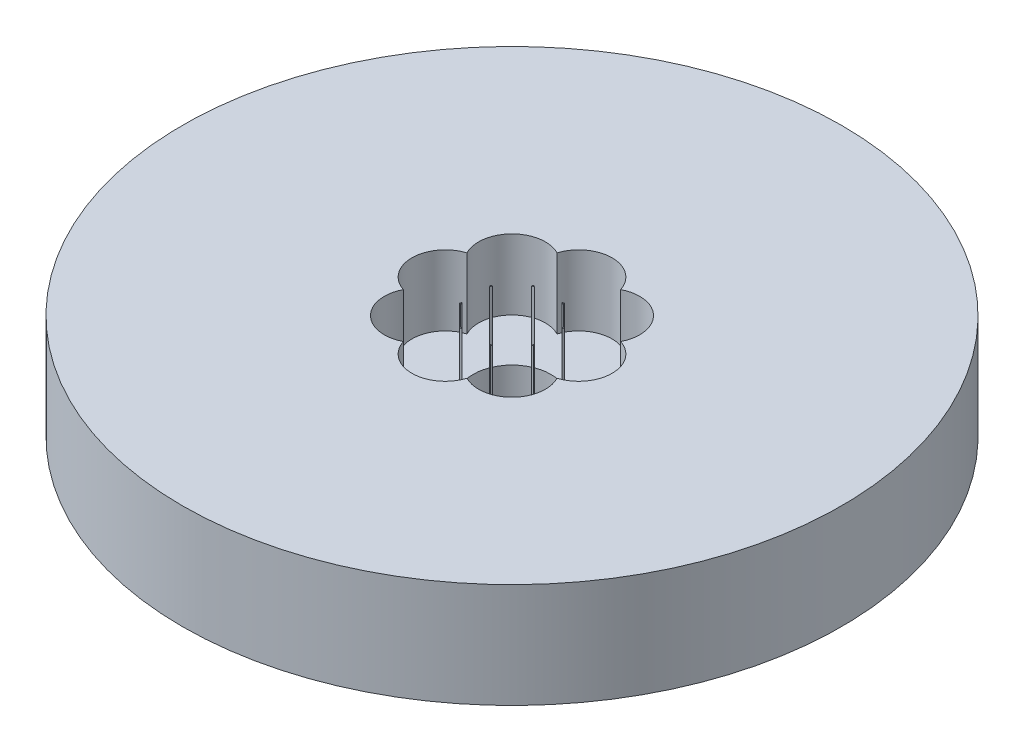
SolidWorks part; units mm, degrees
ref_plane "Front Plane" through (0, 0, 0) normal (0, 0, 1) x (1, 0, 0)
ref_plane "Top Plane" through (0, 0, 0) normal (0, 1, 0) x (1, 0, 0)
ref_plane "Right Plane" through (0, 0, 0) normal (1, 0, 0) x (0, 0, -1)
sketch "Sketch1" plane through (0, 0, 0) normal (0, 1, 0) x (1, 0, 0)
  circle A0 centre (0, 0) radius 85
  dimension "FLANGE_OD" = 170
extrude "Boss-Extrude1" add sketch "Sketch1" along normal blind 27
sketch "Sketch2" plane through (0, 0, 0) normal (0, 1, 0) x (1, 0, 0)
  circle A0 centre (0, 0) radius 10
  dimension "BORE_D" = 20
extrude "Cut-Extrude1" cut sketch "Sketch2" along normal through all
sketch "Sketch3" plane through (0, 27, 0) normal (0, 1, 0) x (1, 0, 0)
  circle A0 centre (0, 0) radius 17.2007 construction
  circle A1 centre (-17.2007, 0) radius 8.6113
  dimension "BOLT_D" = 17.2227
  dimension "BOLT_PCD" = 34.4013
extrude "Cut-Extrude2" cut sketch "Sketch3" against normal blind 18.1211
pattern_circular "CirPattern1" count 8 over 360 about axis through (0, 0, 0) along (0, 1, 0) of "Cut-Extrude2"
